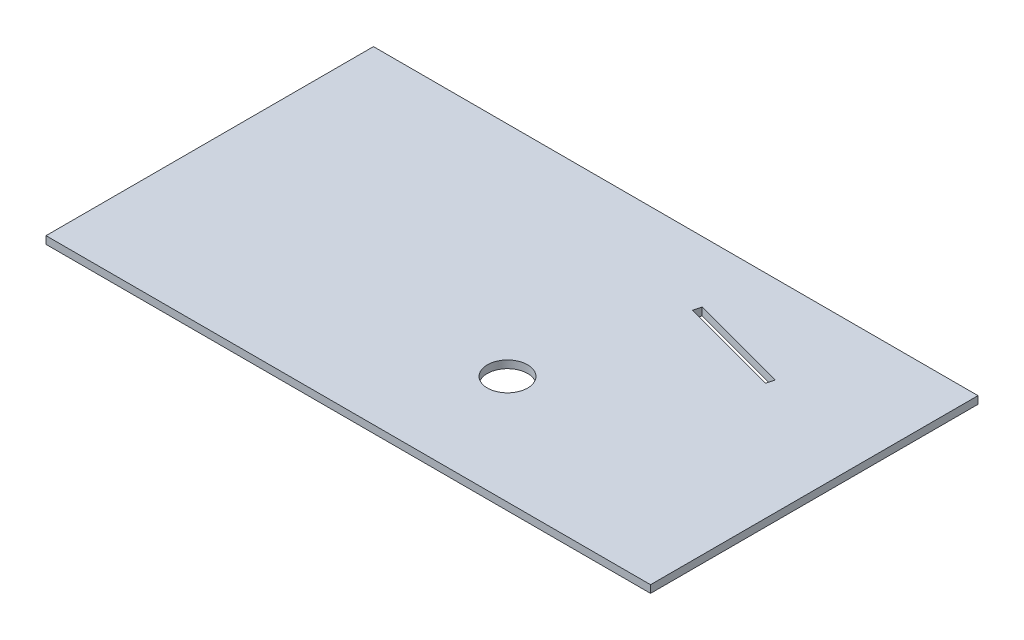
SolidWorks part; units mm, degrees
material "Particle Board"
ref_plane "Front Plane" through (0, 0, 0) normal (0, 0, 1) x (1, 0, 0)
ref_plane "Top Plane" through (0, 0, 0) normal (0, 1, 0) x (1, 0, 0)
ref_plane "Right Plane" through (0, 0, 0) normal (1, 0, 0) x (0, 0, -1)
sketch "Sketch3" plane through (0, 0, 0) normal (0, 1, 0) x (1, 0, 0)
  line L1 (0, 0) -> (-839.8654, 0) construction
  line L2 (0, 0) -> (-451.1992, 260.5) construction
  line L5 (-524, 0) -> (-525.5875, 0)
  line L6 (277.6777, 444.3772) -> (277.6777, 446.248)
  circle A0 centre (0, 0) radius 254 construction
  arc A3 (277.6777, 444.3772) -> (-524, 0) centre (0, 0) ccw
  arc A4 (277.6777, 446.248) -> (-525.5875, 0) centre (0, 0) ccw
  arc A5 (278.5189, 445.7235) -> (-525.5875, 0) centre (0, 0) ccw construction
  dimension "D1" = 524
  dimension "D2" = 1.5875
  dimension "D4" = 122
  dimension "D5" = 508
  dimension "D3" = 30
extrude "Boss-Extrude1" add sketch "Sketch3" along normal blind 50.8
sketch "Sketch4" plane through (0, 50.8, 0) normal (0, 1, 0) x (1, 0, 0)
  line L5 (-889, 551.088) -> (635, 551.088)
  line L6 (-889, 551.088) -> (-889, -274.412)
  line L7 (-889, -274.412) -> (635, -274.412)
  line L8 (635, 551.088) -> (635, -274.412)
  dimension "D1" = 274.412
  dimension "D2" = 1524
  dimension "D3" = 825.5
  dimension "D4" = 635
extrude "Boss-Extrude2" add sketch "Sketch4" along normal blind 19.05
hole_wizard "Ø20.0mm Dowel Hole1" positions "Sketch6" profile "Sketch7" hole size "Ø20.0" standard "ANSI Metric" end condition through all
sketch "Sketch6" plane through (0, 50.8, 0) normal (0, -1, 0) x (-1, 0, 0)
  point P0 (0, 0)
sketch "Sketch7" plane through (0, 50.8, 0) normal (1, 0, 0) x (0, 0, -1)
  line L0 (0, 0) -> (0, 19.05)
  line L1 (0, 19.05) -> (50.8, 19.05)
  line L2 (50.8, 19.05) -> (50.8, 0)
  line L5 (50.8, 0) -> (0, 0)
  line L11 (0, -6.35) -> (0, 107.95) construction
  dimension "Thru Hole Dia." = 101.6
  dimension "Thru Hole Depth" = 19.05
ref_plane "Plane1" through (0, 0, 268.062) normal (0, 0, 1) x (1, 0, 0)
sketch "Sketch8" plane through (0, 0, 0) normal (0, 0, 1) x (1, 0, 0)
  line L0 (-524, 50.8) -> (-524, 0) construction
  line L1 (-525.5875, 50.8) -> (-524, 50.8)
  line L2 (-525.5875, 50.8) -> (-525.5875, 0)
  line L3 (-525.5875, 0) -> (-524, 0)
  line L4 (-524, 50.8) -> (-524, 0)
  line L5 (-525.5875, 50.8) -> (-525.5875, 0) construction
  line L6 (-525.5875, 0) -> (-524, 0) construction
  line L7 (-525.5875, 50.8) -> (-524, 50.8) construction
extrude "Boss-Extrude3" add sketch "Sketch8" along normal blind 204
sketch "Sketch9" plane through (0, 50.8, 0) normal (0, -1, 0) x (-1, 0, 0)
  line L0 (-94.0357, 396.6115) -> (-345.1764, 329.3185)
  line L1 (-345.1764, 329.3185) -> (-340, 310)
  line L2 (-340, 310) -> (-88.8593, 377.293)
  line L3 (-88.8593, 377.293) -> (-94.0357, 396.6115)
  line L6 (0, 0) -> (-635, 0) construction
  line L7 (-635, -274.412) -> (-635, 551.088) construction
  dimension "D1" = 260
  dimension "D2" = 20
  dimension "D3" = 15
  dimension "D4" = 340
  dimension "D5" = 310
extrude "Cut-Extrude1" cut sketch "Sketch9" against normal through all
sketch "Sketch10" plane through (0, 69.85, 0) normal (0, -1, 0) x (-1, 0, 0)
  line L0 (0, 0) -> (-545.6, 0) construction
  line L1 (0, 0) -> (277.6777, 444.3772) construction
  line L2 (0, 0) -> (195.5256, 509.3615) construction
  line L3 (0, 0) -> (94.7424, 537.3111) construction
  circle A0 centre (0, 0) radius 545.6 construction
  dimension "D1" = 11
  dimension "D2" = 11
ref_axis "WHEEL CENTER" through (-565.7508, 50.8, 0) along (1, 0, 0)
ref_plane "BASE CENTER" through (-127, 0, 0) normal (1, 0, 0) x (0, 0, -1)
sketch "Sketch11" plane through (0, 50.8, 0) normal (0, -1, 0) x (1, 0, 0)
  line L0 (240.5176, 138.2676) -> (268.3331, 149.5058)
  line L1 (268.3331, 149.5058) -> (296.8782, 78.8544)
  line L2 (296.8782, 78.8544) -> (269.0626, 67.6162)
  line L3 (269.0626, 67.6162) -> (240.5176, 138.2676)
  line L4 (-561.4964, -185.7671) -> (-532.9514, -256.4185)
  line L5 (-532.9514, -256.4185) -> (-505.1359, -245.1803)
  line L6 (-505.1359, -245.1803) -> (-533.6809, -174.5289)
  line L7 (-533.6809, -174.5289) -> (-561.4964, -185.7671)
  line L8 (-889, -259.242) -> (635, -259.242)
  line L9 (635, 274.412) -> (635, -551.088) construction
  line L10 (-889, -551.088) -> (-889, 274.412) construction
  line L11 (635, -551.088) -> (-889, -551.088) construction
  dimension "D1" = 30
  dimension "D2" = 30
  dimension "D3" = 291.846
